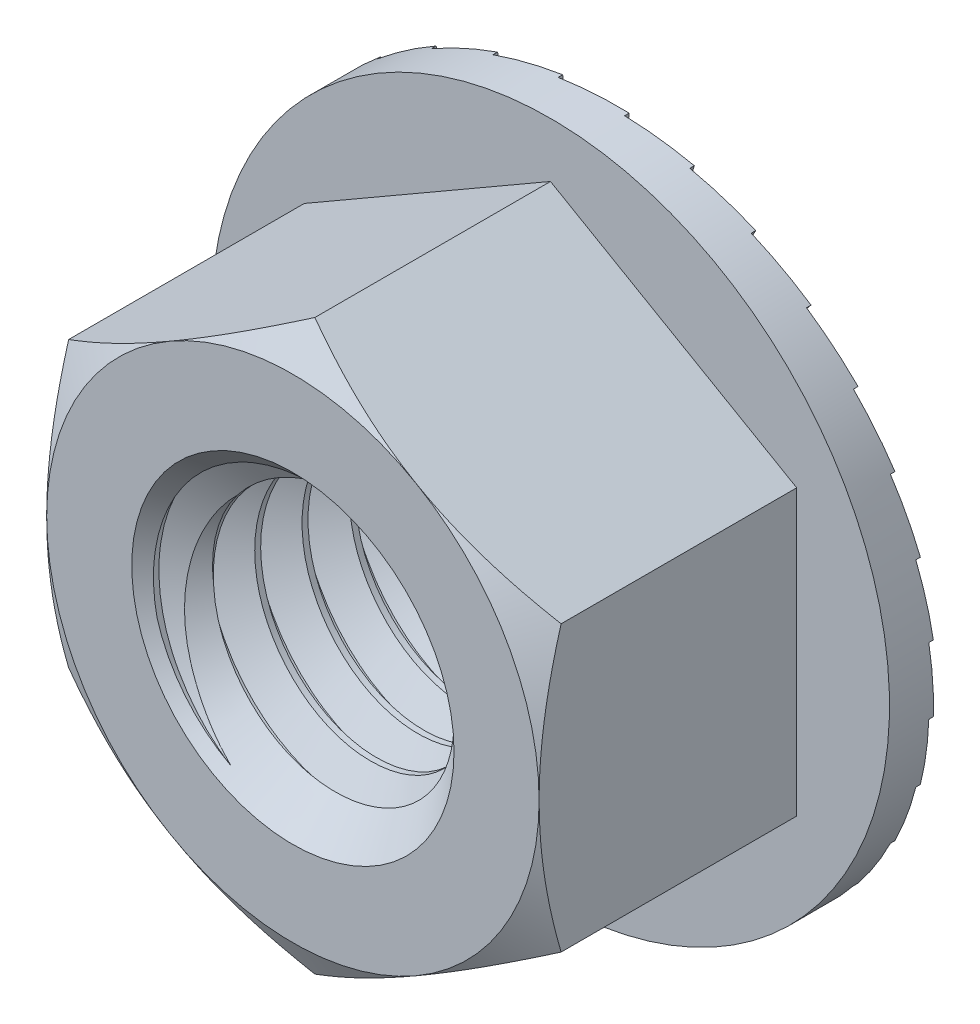
SolidWorks part; units mm, degrees
ref_plane "Front Plane" through (0, 0, 0) normal (0, 0, 1) x (1, 0, 0)
ref_plane "Top Plane" through (0, 0, 0) normal (0, 1, 0) x (1, 0, 0)
ref_plane "Right Plane" through (0, 0, 0) normal (1, 0, 0) x (0, 0, -1)
sketch "Sketch1" plane through (0, 0, 0) normal (0, 0, 1) x (1, 0, 0)
  line L1 (0, 7.5056) -> (-6.5, 3.7528)
  line L2 (-6.5, 3.7528) -> (-6.5, -3.7528)
  line L3 (-6.5, -3.7528) -> (0, -7.5056)
  line L4 (0, -7.5056) -> (6.5, -3.7528)
  line L5 (6.5, -3.7528) -> (6.5, 3.7528)
  line L6 (6.5, 3.7528) -> (0, 7.5056)
  circle A0 centre (0, 0) radius 6.5 construction
  dimension "Hex" = 13
extrude "Extrude1" add sketch "Sketch1" against normal blind 8
sketch "Sketch13" plane through (0, 0, -8) normal (0, 0, -1) x (-1, 0, 0)
  circle A0 centre (0, 0) radius 8.95
  dimension "Flange od" = 17.9
extrude "Extrude3" add sketch "Sketch13" against normal blind 1.2
sketch "Sketch2" plane through (0, 0, 0) normal (0, 0, 1) x (1, 0, 0)
  circle A0 centre (0, 0) radius 6.5 construction
  circle A1 centre (0, 0) radius 6.5
extrude "Cut-Extrude1" cut sketch "Sketch2" against normal through all draft 60 flip side to cut
sketch "Sketch4" plane through (0, 0, 0) normal (0, 0, 1) x (1, 0, 0)
  circle A0 centre (0, 0) radius 4
  dimension "Thread Dia" = 8
extrude "Cut-Extrude3" cut sketch "Sketch4" against normal through all
sketch "Sketch7" plane through (0, 0, 0) normal (0, 0, 1) x (1, 0, 0)
  circle A4 centre (0, 0) radius 4.254
  circle A5 centre (0, 0) radius 4.254
  dimension "D1" = 0.254
sketch "Sketch8" plane through (0, 0, -8) normal (0, 0, -1) x (-1, 0, 0)
  circle A1 centre (0, 0) radius 4.254
  circle A2 centre (0, 0) radius 4.254 construction
sketch "Sketch5" plane through (0, 0, 0) normal (0, 0, 1) x (1, 0, 0)
  circle A0 centre (0, 0) radius 4 construction
  circle A1 centre (0, 0) radius 4
curve "Helix/Spiral1" pitch 1.25 height 9.25 turns 7.4 parameters "pitch"=1.25
sketch "Sketch9" plane through (0, 0, 0) normal (1, 0, 0) x (0, 0, -1)
  line L0 (-0.625, 4) -> (-0.4688, 4)
  line L1 (-0.4688, 4) -> (0, 3.1881)
  line L2 (-0.625, 4) -> (-1.0938, 3.1881)
  line L3 (-1.0938, 3.1881) -> (0, 3.1881)
  line L4 (-0.5469, 4) -> (-0.5469, 3.1881) construction
  line L5 (-0.8594, 3.5941) -> (-0.2344, 3.5941) construction
  line L7 (0, 3.1881) -> (0, 4) construction
  line L8 (0, 4) -> (0, -4) construction
  dimension "D1" = 0.1562
  dimension "D2" = 0.625
  dimension "D3" = 60
sketch "Sketch12" plane through (0, 0, 0) normal (0, 0, 1) x (1, 0, 0)
  circle A0 centre (0, 0) radius 3.1881
  circle A1 centre (0, 0) radius 4 construction
  circle A2 centre (0, 0) radius 4
extrude "Extrude2" add sketch "Sketch12" against normal up to surface (8 mm away) up to face at (4, 0, -8)
sweep "Cut-Sweep1" cut profiles "Sketch9" path "Helix/Spiral1" align with end faces yes
extrude "Cut-Extrude6" cut sketch "Sketch7" against normal through all draft 45
extrude "Cut-Extrude7" cut sketch "Sketch8" against normal through all draft 45
sketch "Sketch14" plane through (0, 0, -8) normal (0, 0, -1) x (-1, 0, 0)
  circle A4 centre (0, 0) radius 6.286
  circle A5 centre (0, 0) radius 6.286
  dimension "D1" = 2.032
extrude "Cut-Extrude8" cut sketch "Sketch14" against normal blind 0.12 flip side to cut
sketch "Sketch15" plane through (0, 0, -7.88) normal (0, 0, -1) x (-1, 0, 0)
  line L0 (-0.6161, 6.2557) -> (-0.8773, 8.9069)
  line L1 (0.6161, 6.2557) -> (0.8773, 8.9069)
  line L2 (0, 0) -> (0.6161, 6.2557) construction
  line L3 (0, 0) -> (-0.6161, 6.2557) construction
  circle A0 centre (0, 0) radius 8.95 construction
  circle A1 centre (0, 0) radius 6.286 construction
  arc A2 (0.8773, 8.9069) -> (-0.8773, 8.9069) centre (0, 0) ccw
  arc A3 (0.6161, 6.2557) -> (-0.6161, 6.2557) centre (0, 0) ccw
  dimension "D1" = 11.25
extrude "Extrude4" add sketch "Sketch15" along normal up to surface (0.12 mm away) separate body up to face at (-4.254, 0, -8)
sketch "Sketch16" plane through (0, 0, 0) normal (0, 1, 0) x (1, 0, 0)
  line L0 (-0.8773, 7.88) -> (0.8773, 8)
  line L4 (-0.8773, 7.88) -> (0.8773, 7.88)
  line L5 (0.8773, 7.88) -> (0.8773, 8)
  line L6 (0.8773, 8) -> (-0.8773, 8)
  line L7 (-0.8773, 8) -> (-0.8773, 7.88)
  line L8 (-0.8773, 7.88) -> (0.8773, 7.88) construction
  line L9 (0.8773, 7.88) -> (0.8773, 8) construction
  line L10 (0.8773, 8) -> (-0.8773, 8)
  line L11 (-0.8773, 8) -> (-0.8773, 7.88)
  dimension "D1" = 0
extrude "Cut-Extrude9" cut sketch "Sketch16" along normal through all
pattern_circular "CirPattern1" count 32 over 360 about axis through (0, 0, 0) along (0, 0, 1) of bodies 119
combine bodies "Combine1" operation type add bodies to combine 117 119 120 121 122 123 124 125 126 127 128 129 130 131 132 133 134 135 136 137 139 140 141 142 143 144 145 146 147 148 149 150 151
sketch "Sketch17" plane through (0, 0, 0) normal (1, 0, 0) x (0, 0, -1)
  line L0 (8, 8.95) -> (8, -8.95) construction
  line L1 (6.8, 8.95) -> (6.8, -8.95) construction
  dimension "D1" = 1.2
sketch "Sketch18" plane through (0, 0, -6.8) normal (0, 0, 1) x (1, 0, 0)
  circle A0 centre (0, 0) radius 8.95
  circle A1 centre (0, 0) radius 8.95 construction
equation "\"D2@Sketch9\" = \"pitch@Helix/Spiral1\"*.5"
equation "\"D3@Helix/Spiral1\" = \"pitch@Helix/Spiral1\"+\"Height@Extrude1\""
equation "\"D1@Sketch9\" = \"pitch@Helix/Spiral1\"*.125"
equation "\"D1@Cut-Extrude8\" = \"flange thickness@Extrude3\"*.1"
equation "\"D1@Sketch17\" = \"flange thickness@Extrude3\""
